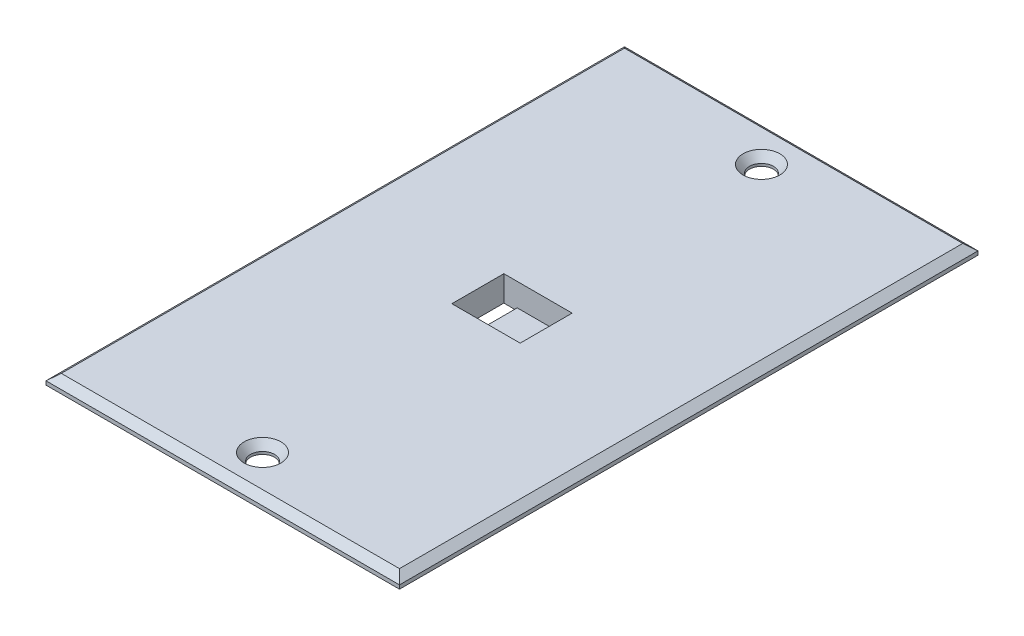
SolidWorks part; units mm, degrees
ref_plane "Front Plane" through (0, 0, 0) normal (0, 0, 1) x (1, 0, 0)
ref_plane "Top Plane" through (0, 0, 0) normal (0, 1, 0) x (1, 0, 0)
ref_plane "Right Plane" through (0, 0, 0) normal (1, 0, 0) x (0, 0, -1)
sketch "Sketch1" plane through (0, 0, 0) normal (0, 1, 0) x (1, 0, 0)
  line L1 (-34.675, 56.75) -> (34.675, 56.75)
  line L2 (-34.675, 56.75) -> (-34.675, -56.75)
  line L3 (-34.675, -56.75) -> (34.675, -56.75)
  line L4 (34.675, 56.75) -> (34.675, -56.75)
  line L5 (-34.675, 56.75) -> (34.675, -56.75) construction
  line L6 (-34.675, -56.75) -> (34.675, 56.75) construction
  point P0 (0, 0)
  dimension "D1" = 113.5
  dimension "D2" = 69.35
extrude "Boss-Extrude5" add sketch "Sketch1" along normal blind 2 contours L2 L1 L4 L3
sketch "Sketch2" plane through (0, 2, 0) normal (0, 1, 0) x (1, 0, 0)
  line L0 (0, 56.75) -> (0, -56.75) construction
  line L1 (-34.675, 56.75) -> (34.675, 56.75) construction
  line L2 (-34.675, -56.75) -> (34.675, -56.75) construction
  line L3 (-34.675, 0) -> (34.675, 0) construction
  line L4 (-34.675, 56.75) -> (-34.675, -56.75) construction
  line L5 (34.675, 56.75) -> (34.675, -56.75) construction
  circle A0 centre (0, 48.9431) radius 2.35
  circle A1 centre (0, -48.9431) radius 2.35
extrude "Cut-Extrude3" cut sketch "Sketch2" against normal blind 2.5
chamfer "face chamfer" distance 1.5 angle 40 6 edges at (0, 2, 46.5931) (0, 2, -46.5931) (0, 2, -56.75) (34.675, 2, 0) (0, 2, 56.75) (-34.675, 2, 0)
sketch "Sketch4" plane through (0, 0, 0) normal (0, -1, 0) x (-1, 0, 0)
  line L1 (-30.1192, 45.2572) -> (30.1192, 45.2572)
  line L2 (-30.1192, 45.2572) -> (-30.1192, -45.2572)
  line L3 (-30.1192, -45.2572) -> (30.1192, -45.2572)
  line L4 (30.1192, 45.2572) -> (30.1192, -45.2572)
  line L5 (-30.1192, 45.2572) -> (30.1192, -45.2572) construction
  line L6 (-30.1192, -45.2572) -> (30.1192, 45.2572) construction
  point P0 (0, 0)
  point P5 (-30.1192, -45.2572)
extrude "Cut-Extrude6" cut sketch "Sketch4" against normal blind 1.5
sketch "Sketch5" plane through (0, 2, 0) normal (0, 1, 0) x (1, 0, 0)
  line L0 (-33.175, 0) -> (33.175, 0) construction
  line L1 (-33.175, 55.25) -> (-33.175, -55.25) construction
  line L2 (33.175, -55.25) -> (33.175, 55.25) construction
  line L3 (0, 55.25) -> (0, -56.75) construction
  line L4 (33.175, 55.25) -> (-33.175, 55.25) construction
  line L5 (34.675, -56.75) -> (-34.675, -56.75) construction
  line L7 (-6.7, 5.1) -> (6.7, 5.1)
  line L8 (-6.7, 5.1) -> (-6.7, -5.1)
  line L9 (-6.7, -5.1) -> (6.7, -5.1)
  line L10 (6.7, 5.1) -> (6.7, -5.1)
  line L11 (-6.7, 5.1) -> (6.7, -5.1) construction
  line L12 (-6.7, -5.1) -> (6.7, 5.1) construction
  line L13 (10.4666, 8.5495) -> (-10.4666, 8.5495)
  line L14 (10.4666, 8.5495) -> (10.4666, -8.5495)
  line L15 (10.4666, -8.5495) -> (-10.4666, -8.5495)
  line L16 (-10.4666, 8.5495) -> (-10.4666, -8.5495)
  line L17 (10.4666, 8.5495) -> (-10.4666, -8.5495) construction
  line L18 (10.4666, -8.5495) -> (-10.4666, 8.5495) construction
  point P12 (0, 0)
  point P17 (0, 0)
  dimension "D1" = 13.4
  dimension "D2" = 10.2
extrude "Boss-Extrude7" add sketch "Sketch5" against normal blind 4.5
sketch "Sketch6" plane through (0, 2, 0) normal (0, 1, 0) x (1, 0, 0)
  line L0 (0, 55.25) -> (0, -56.75) construction
  line L1 (33.175, 55.25) -> (-33.175, 55.25) construction
  line L2 (34.675, -56.75) -> (-34.675, -56.75) construction
  line L3 (-34.675, 0) -> (34.675, 0) construction
  line L4 (-34.675, -56.75) -> (-34.675, 56.75) construction
  line L5 (34.675, 56.75) -> (34.675, -56.75) construction
  line L7 (-6.7, 5.1) -> (6.7, 5.1)
  line L8 (-6.7, 5.1) -> (-6.7, -5.1)
  line L9 (-6.7, -5.1) -> (6.7, -5.1)
  line L10 (6.7, 5.1) -> (6.7, -5.1)
  line L11 (-6.7, 5.1) -> (6.7, -5.1) construction
  line L12 (-6.7, -5.1) -> (6.7, 5.1) construction
  point P12 (0, 0)
  dimension "D1" = 13.4
  dimension "D2" = 10.2
extrude "Cut-Extrude7" cut sketch "Sketch6" against normal blind 4.1
sketch "Sketch7" plane through (0, -2.5, 0) normal (0, -1, 0) x (1, 0, 0)
  line L1 (-10.4666, 8.5495) -> (10.4666, 8.5495)
  line L2 (-10.4666, 8.5495) -> (-10.4666, -8.5495)
  line L3 (-10.4666, -8.5495) -> (10.4666, -8.5495)
  line L4 (10.4666, 8.5495) -> (10.4666, -8.5495)
  line L5 (-10.4666, 8.5495) -> (10.4666, -8.5495) construction
  line L6 (-10.4666, -8.5495) -> (10.4666, 8.5495) construction
  point P0 (0, 0)
extrude "Boss-Extrude8" add sketch "Sketch7" along normal blind 0.5
sketch "Sketch8" plane through (0, -2.5, 0) normal (0, 1, 0) x (1, 0, 0)
  line L0 (-6.7, -5.1) -> (6.7, -5.1) construction
  line L1 (-6.7, 5.1) -> (-4.0786, 5.1)
  line L2 (-6.7, 5.1) -> (-6.7, -5.1)
  line L3 (-6.7, -5.1) -> (-4.0786, -5.1)
  line L4 (-4.0786, 5.1) -> (-4.0786, -5.1)
extrude "Cut-Extrude8" cut sketch "Sketch8" against normal blind 0.5
ref_plane "Plane4" through (6.7, 0, 0) normal (1, 0, 0) x (0, 0, -1)
sketch "Sketch10" plane through (6.7, 0, 0) normal (-1, 0, 0) x (0, 0, 1)
  line L0 (0, 2) -> (0, -2.5) construction
  line L1 (5.1, 2) -> (-5.1, 2) construction
  line L2 (5.1, -2.5) -> (-5.1, -2.5) construction
  line L3 (-5.1, 0.3) -> (5.1, 0.3) construction
  line L4 (-5.1, -2.5) -> (-5.1, 2) construction
  line L5 (5.1, -2.5) -> (5.1, 2) construction
  line L7 (-0.6375, 0.3) -> (0.5457, 0.3)
  line L8 (-0.6375, 0.3) -> (-0.6375, 0.9608)
  line L9 (-0.6375, 0.9608) -> (0.5457, 0.9608)
  line L10 (0.5457, 0.3) -> (0.5457, 0.9608)
  dimension "D1" = 2.8
extrude "Boss-Extrude11" add sketch "Sketch10" along normal blind 1
fillet "Fillet1" radius 0.9 1 edges at (5.7, 0.9608, -0.0459)
